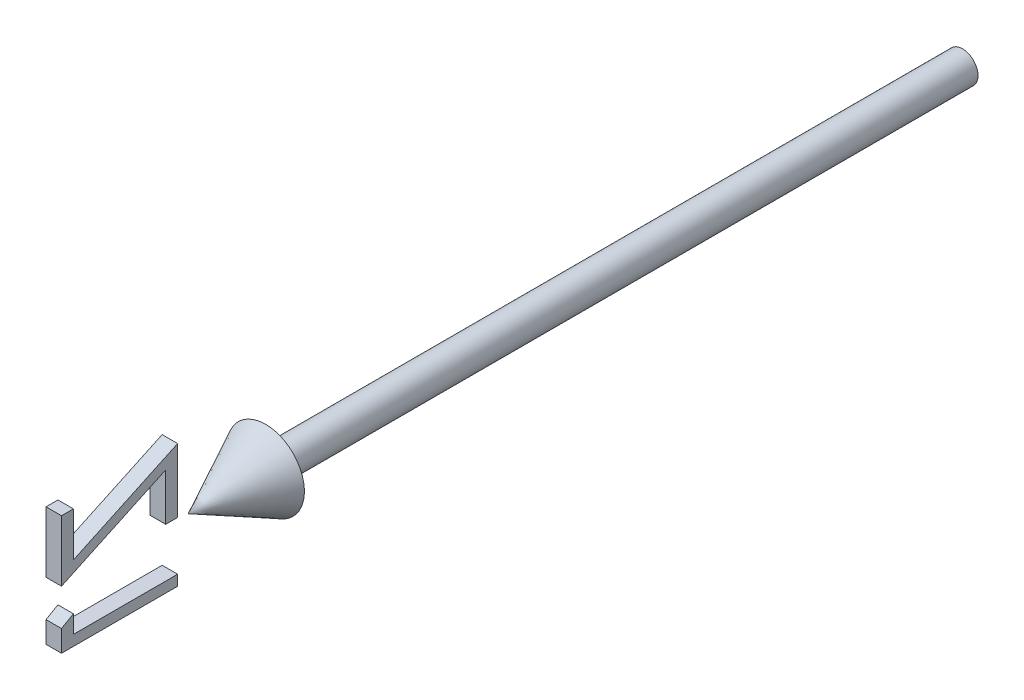
SolidWorks part; units mm, degrees
ref_plane "Front Plane" through (0, 0, 0) normal (0, 0, 1) x (1, 0, 0)
ref_plane "Top Plane" through (0, 0, 0) normal (0, 1, 0) x (1, 0, 0)
ref_plane "Right Plane" through (0, 0, 0) normal (1, 0, 0) x (0, 0, -1)
sketch "Sketch2" plane through (0, 0, 0) normal (0, 1, 0) x (1, 0, 0)
  line L0 (0, 41.95) -> (0, -114.4521) construction
  line L1 (-36.8894, 0) -> (41.4965, 0) construction
  line L2 (0, -100) -> (5, -90)
  line L3 (5, -90) -> (2, -90)
  line L4 (2, -90) -> (2, 0)
  line L5 (2, 0) -> (0, 0)
  line L6 (0, 0) -> (0, -100)
  dimension "D1" = 100
  dimension "D2" = 2
  dimension "D3" = 10
  dimension "D4" = 5
revolve "Revolve1" add sketch "Sketch2" angle 360 about L0
sketch "Sketch3" plane through (0, 0, 0) normal (1, 0, 0) x (0, -1, 0)
  line L0 (0, -101.5706) -> (0, -127.8138) construction
  line L1 (-10.1124, -102.3675) -> (14.1256, -102.3675) construction
  text T0 "Z1" font "Century Gothic" height 15
extrude "Boss-Extrude1" add sketch "Sketch3" against normal blind 1 and the other way blind 1 separate body
equation "\"frame_arrow_length\"=100"
equation "\"D1@Sketch2\"=\"frame_arrow_length\""
equation "\"frame_arrow_odA\"=4"
equation "\"D2@Sketch2\"=\"frame_arrow_odA\"/2"
equation "\"frame_arrow_head_od\"=5"
equation "\"D4@Sketch2\"=\"frame_arrow_head_od\""
equation "\"frame_arrow_head_length\"=10"
equation "\"D3@Sketch2\"=\"frame_arrow_head_length\""
equation "\"tvarobot_theta1\"=30"
equation "\"link0_ringA_odA\"= 40"
equation "\"link0_ringA_odB\"= 25"
equation "\"link0_ringA_id\"= 20"
equation "\"link0_ringA_thickness\"= (\"link0_ringA_odB\" - \"link0_ringA_id\")/2"
equation "\"link0_ringA_height\"= 3"
equation "\"link0_ringA_heightA\"= 1.5"
equation "\"link0_ringA_heightB\"=\"link0_ringA_height\"-\"link0_ringA_heightA\""
equation "\"link0_ringB_odA\"= 40"
equation "\"link0_ringB_odB\"= 29"
equation "\"link0_ringB_id\"= \"link0_shaftA_bearing_id\"+1"
equation "\"link0_ringB_thickness\"= (\"link0_ringB_odB\" - \"link0_ringB_id\")/2"
equation "\"link0_ringB_height\"= 3"
equation "\"link0_ringB_heightA\"= 1.5"
equation "\"link0_ringB_heightB\"=\"link0_ringB_height\"-\"link0_ringB_heightA\""
equation "\"link0_shaftA_bearing_od\"=27"
equation "\"link0_shaftA_bearing_id\"=20"
equation "\"link0_shaftA_thrust_bearing_od\"=35"
equation "\"link0_shaftA_thrust_bearing_id\"=20.04"
equation "\"link0_shaftA_retaining_ring_id\"=18.5"
equation "\"link0_shaftA_retaining_ring_groove_width\"=1.5"
equation "\"link0_shaftA_spline_length\"=8.0"
equation "\"link0_shaftA_spline_depth\"=1.0"
equation "\"link0_shaftA_spline_width\"=4.0"
equation "\"link0_shaftA_odA\"=\"link0_shaftA_bearing_id\""
equation "\"link0_shaftA_odB\"=35"
equation "\"link0_shaftA_odC\"=\"link0_shaftA_bearing_id\""
equation "\"link0_shaftA_odD\"=\"link0_shaftA_odC\"-2*\"link0_shaftA_spline_depth\""
equation "\"link0_shaftA_odE\"=\"link0_shaftA_bearing_id\""
equation "\"link0_shaftA_odF\"=\"link0_shaftA_odE\"-2*\"link0_shaftA_spline_depth\""
equation "\"link0_shaftA_idA\"=10"
equation "\"link0_shaftA_idB\"=6"
equation "\"link0_shaftA_length\"=39.5"
equation "\"link0_shaftA_lengthA\"=8.0"
equation "\"link0_shaftA_lengthB\"=12.0"
equation "\"link0_shaftA_lengthC\"=35.0"
equation "\"link0_shaftA_lengthD\"=39.0"
equation "\"link0_shaftA_lengthE\"=\"link0_shaftA_length\"-\"link0_shaftA_lengthD\""
equation "\"link0_shaftA_offsetX\"=11"
equation "\"link0_shaftA_offsetY\"=0"
equation "\"link0_shaftA_bolt_pattern_dia\"=14"
equation "\"link0_motor_center_dist\"=26"
equation "\"link0_46t_pulley_spline_length\"=8"
equation "\"link0_46t_pulley_spline_depth\"=\"link0_shaftA_spline_depth\"*1.025"
equation "\"link0_46t_pulley_spline_width\"=\"link0_shaftA_spline_width\"*1.05"
equation "\"link0_46t_pulley_idA\"=\"link0_shaftA_bearing_id\"*1.025"
equation "\"link0_46t_pulley_idB\"=\"link0_46t_pulley_idA\"-2*\"link0_46t_pulley_spline_depth\""
equation "\"link0_shaftB_spline_length\"=10"
equation "\"link0_shaftB_spline_depth\"=1.0"
equation "\"link0_shaftB_spline_width\"=1.25"
equation "\"link0_shaftB_length\"=7"
equation "\"link0_shaftB_lengthA\"=1.5"
equation "\"link0_shaftB_lengthB\"=2.75"
equation "\"link0_shaftB_odA\"=32"
equation "\"link0_shaftB_odB\"=22"
equation "\"link0_shaftB_odC\"=20"
equation "\"link0_shaftB_idA\"=10"
equation "\"link0_shaftB_bolt_diameter\"=19"
equation "\"link0_shaftB_bearing_od\"=27"
equation "\"link0_shaftB_bearing_id\"=20"
equation "\"link0_motor_length\"=46.5"
equation "\"link0_motor_width\"=28.5"
equation "\"link0_motor_height\"=34"
equation "\"link0_motor_offset\"=8"
equation "\"link0_shellA_thickness\"=2.5"
equation "\"link0_shellB_thickness\"=\"link0_shellA_thickness\""
equation "\"link0_plateA_shellA_height\"=48"
equation "\"link0_shellA_width\" =\"link0_plateA_width\""
equation "\"link0_shellA_height\" = \"link0_plateA_shellA_height\"-\"link0_plateA_height\""
equation "\"link0_shellA_length\" = \"link0_plateA_lengthB\" "
equation "\"link0_shellB_length\"=\"link0_shellA_length\""
equation "\"link0_shellA_radius\" = 0.375*25.4"
equation "\"link0_shellA_radiusA\"= \"link0_plateA_radiusA\""
equation "\"link0_shellA_radiusB\"= \"link0_plateA_radiusB\""
equation "\"link0_shellA_radiusC\"= 3"
equation "\"link0_postA_height\"=7"
equation "\"link0_postA_width\"=16"
equation "\"link0_postA_length\"=20"
equation "\"link0_postA_posX\"=22"
equation "\"link0_postA_posY\"=17.5"
equation "\"link0_postA_pocket_width\"=6.0"
equation "\"link0_postA_pocket_length\"=2.5"
equation "\"link0_postA_pocket_depth\"=9"
equation "\"link0_postA_pocket_posZ\"=10"
equation "\"link0_postB_height\"=7"
equation "\"link0_postB_width\"=16"
equation "\"link0_postB_length\"=20"
equation "\"link0_postB_posX\"=22"
equation "\"link0_postB_posY\"=17.5"
equation "\"link0_postB_id\"=3.0"
equation "\"link0_postB_pocket_width\"=6.0"
equation "\"link0_postB_pocket_length\"=2.5"
equation "\"link0_postB_pocket_depth\"=9"
equation "\"link0_postB_pocket_posZ\"=10"
equation "\"link0_postC_height\"=7"
equation "\"link0_postC_width\"=16"
equation "\"link0_postC_length\"=20"
equation "\"link0_postC_posX\"=22"
equation "\"link0_postC_posY\"=17.5"
equation "\"link0_postC_id\"=3.0"
equation "\"link0_postC_pocket_width\"=6.0"
equation "\"link0_postC_pocket_length\"=2.5"
equation "\"link0_postC_pocket_depth\"=9"
equation "\"link0_postC_pocket_posZ\"=10"
equation "\"link0_postD_height\"=7"
equation "\"link0_postD_width\"=16"
equation "\"link0_postD_length\"=20"
equation "\"link0_postD_posX\"=22"
equation "\"link0_postD_posY\"=17.5"
equation "\"link0_postD_id\"=3.0"
equation "\"link0_postD_pocket_width\"=6.0"
equation "\"link0_postD_pocket_length\"=3.0"
equation "\"link0_postD_pocket_depth\"=9"
equation "\"link0_postD_pocket_posZ\"=10"
equation "\"link0_postE_height\"=5"
equation "\"link0_postE_width\"=16"
equation "\"link0_postE_length\"=\"link0_plateE_lengthA\"-\"link0_lip_height\""
equation "\"link0_postE_posZ\"=22"
equation "\"link0_postE_posX\"=17.5"
equation "\"link0_postE_posY\"=22"
equation "\"link0_postE_id\"=3.0"
equation "\"link0_postE_cbore_id\"=6.5"
equation "\"link0_postE_hole_id\"=3"
equation "\"link0_postF_posZ\"=22"
equation "\"link0_postF_posX\"=17.5"
equation "\"link0_postF_posY\"=\"link0_plateB_lengthA\"+4"
equation "\"link0_postF_id\"=3.0"
equation "\"link0_postF_cbore_id\"=6.5"
equation "\"link0_postF_hole_id\"=3"
equation "\"link0_postG_posZ\"=22"
equation "\"link0_postG_posX\"=17.5"
equation "\"link0_postG_posY\"=\"link0_plateB_lengthA\"+12"
equation "\"link0_postG_id\"=3.0"
equation "\"link0_postG_cbore_id\"=6.5"
equation "\"link0_postG_hole_id\"=3"
equation "\"link0_postHIJ_posY\"=6"
equation "\"link0_postH_posX\"=28"
equation "\"link0_postH_posY\"=20"
equation "\"link0_postH_posZ\"=20"
equation "\"link0_postH_length\"=10"
equation "\"link0_postI_posX\"=28"
equation "\"link0_postI_posY\"=20"
equation "\"link0_postI_posZ\"=135"
equation "\"link0_postI_length\"=10"
equation "\"link0_postJ_posX\"=28"
equation "\"link0_postJ_posY\"=20"
equation "\"link0_postJ_posZ\"=175"
equation "\"link0_postJ_length\"=10"
equation "\"link0_postK_posX\"=28"
equation "\"link0_postK_posY\"=20"
equation "\"link0_postK_posZ\"=175"
equation "\"link0_postK_length\"=10"
equation "\"link0_postL_posX\"=28"
equation "\"link0_postL_posY\"=20"
equation "\"link0_postL_posZ\"=135"
equation "\"link0_postL_length\"=10"
equation "\"link0_postM_posX\"=28"
equation "\"link0_postM_posY\"=20"
equation "\"link0_postM_posZ\"=35"
equation "\"link0_postM_length\"=10"
equation "\"link0_plateA_lengthA\"=30"
equation "\"link0_plateA_lengthB\"=150"
equation "\"link0_plateA_lengthC\"=30"
equation "\"link0_plateA_length\"=\"link0_plateA_lengthA\"+\"link0_plateA_lengthB\"+\"link0_plateA_lengthC\""
equation "\"link0_plateA_width\"=  68"
equation "\"link0_plateA_height\"= \"link0_plateA_radiusA\""
equation "\"link0_plateA_thickness\"=\"link0_shellA_thickness\""
equation "\"link0_plateA_radius\"= 9.5"
equation "\"link0_plateA_radiusA\"= 18"
equation "\"link0_plateA_radiusB\"= 18"
equation "\"link0_plateA_radiusC\"= 3"
equation "\"link0_plateB_length\"= 40"
equation "\"link0_plateB_width\"= \"link0_plateA_width\"*1.005"
equation "\"link0_plateB_height\"= \"link0_plateA_shellA_height\"*1.005"
equation "\"link0_plateB_lengthA\"=\"link0_lip_height\"+\"link0_plateD_thickness\"+\"link0_motor_mount_thickness\""
equation "\"link0_plateB_lengthB\"=\"link0_plateB_height\"-\"link0_plateB_lengthA\""
equation "\"link0_plateB_radiusA\"= \"link0_plateA_radiusA\""
equation "\"link0_plateB_radiusB\"= \"link0_plateA_radiusB\""
equation "\"link0_plateB_radiusC\"= 3"
equation "\"link0_plateB_idA\"=\"link0_shaftA_odC\"+1"
equation "\"link0_plateB_idB\"=\"link0_shaftA_bearing_od\"-2"
equation "\"link0_plateB_idC\"=\"link0_shaftA_bearing_od\"*1.005"
equation "\"link0_plateB_idD\"=\"link0_shaftA_thrust_bearing_od\"+1 "
equation "\"link0_plateB_depthA\"=1.0"
equation "\"link0_plateB_depthB\"=2.0"
equation "\"link0_plateB_depthC\"=8"
equation "\"link0_plateB_depthD\"=\"link0_plateB_length\"-\"link0_lip_height\"-\"link0_plateD_thickness\" "
equation "\"link0_plateC_length\"=\"link0_plateB_length\""
equation "\"link0_plateC_width\"= \"link0_plateB_width\""
equation "\"link0_plateC_height\"= .1*25.4"
equation "\"link0_plateA_hole_od\" = 0.1*25.4"
equation "\"link0_plateA_hole_delx\" = 0.5*25.4"
equation "\"link0_plateA_hole_delz\" = 0.75*25.4"
equation "\"link0_plateA_hole_offx\" = 0.0*25.4"
equation "\"link0_plateA_hole_offz\" = \"link0_plateA_length\"/2"
equation "\"link0_plateB_hole_od\" = 0.1*25.4"
equation "\"link0_plateB_hole_delx\"= 0.75*25.4"
equation "\"link0_plateB_hole_delz\"= 0.75*25.4"
equation "\"link0_plateB_hole_offx\"= 0.0*25.4"
equation "\"link0_plateB_hole_offz\"= 0.0*25.4"
equation "\"link0_plateC_hole_od\"= 0.1*25.4"
equation "\"link0_plateC_hole_delx\"= 0.75*25.4"
equation "\"link0_plateC_hole_delz\"= 0.75*25.4"
equation "\"link0_plateC_hole_offx\"= 0.0*25.4"
equation "\"link0_plateC_hole_offz\"= 0.0*25.4"
equation "\"link0_plateD_height\"=\"link0_plateB_height\"-2*\"link0_shellA_thickness\""
equation "\"link0_plateD_width\"=\"link0_plateB_width\"-2*\"link0_shellA_thickness\""
equation "\"link0_plateD_thickness\"=10"
equation "\"link0_plateD_radiusA\"=\"link0_plateB_radiusA\"-\"link0_shellA_thickness\""
equation "\"link0_plateD_odA\"= .375*25.4"
equation "\"link0_plateD_odB\"= .375*25.4"
equation "\"link0_plateD_bearing_id\"=20"
equation "\"link0_plateD_bearing_od\"=27"
equation "\"link0_plateE_radiusA\"=\"link0_plateA_radiusA\""
equation "\"link0_plateE_radiusB\"=\"link0_plateA_radiusB\""
equation "\"link0_plateE_radiusC\"=8.0"
equation "\"link0_plateE_length\"=30"
equation "\"link0_plateE_lengthA\"=16"
equation "\"link0_plateE_height\"=\"link0_plateB_height\""
equation "\"link0_plateE_width\"=\"link0_plateB_width\""
equation "\"link0_plateE_odA\"=\"gantry_coupler_id\"*0.99"
equation "\"link0_plateE_idA\"=\"link0_plateE_odA\"-20.0"
equation "\"link0_plateE_spline_depth\"=\"link0_poleA_spline_depth\"*1.05"
equation "\"link0_plateE_spline_width\"=\"link0_poleA_spline_width\"*1.075"
equation "\"link0_plateE_spline_length\"=\"link0_poleA_spline_length\""
equation "\"link0_plateE_coupler_length\"=46"
equation "\"link0_lip_height\"=5.0"
equation "\"link0_lip_thickness\"=2.0"
equation "\"link0_motor_mount_thickness\"=8.0"
equation "\"link0_motor_mount_idA\"=22"
equation "\"link0_motor_mount_idB\"=\"link0_shaftB_bearing_od\"*1.005"
equation "\"link0_motor_mount_idC\"=\"link0_shaftB_bearing_od\"-2"
equation "\"link0_motor_mount_depthA\"=5.5"
equation "\"link0_motor_mount_height\"=\"link0_plateD_height\""
equation "\"link0_motor_mount_width\"=\"link0_plateD_width\""
equation "\"link0_motor_mountL_height\"=36"
equation "\"link0_motor_mountL_heightA\"=12"
equation "\"link0_motor_mountL_length\"=50"
equation "\"link0_motor_mountL_lengthA\"=36"
equation "\"gantry_coupler_od\"=25.4*2.0"
equation "\"gantry_coupler_id\"=1.645*25.4"
equation "\"gantry_coupler_offsetX\"=\"link0_plateE_width\"/2"
equation "\"link0_poleA_odA\"=20"
equation "\"link0_poleA_odB\"=36"
equation "\"link0_poleA_idA\"=\"link0_poleA_odA\"-2*\"link0_poleA_thickness\""
equation "\"link0_poleA_idB\"=(\"link0_plateE_idA\"/2+1.5*\"link0_lip_thickness\")*1.04"
equation "\"link0_poleA_thickness\"=3.5"
equation "\"link0_poleA_length\"=100"
equation "\"link0_poleA_lengthA\"=18.5"
equation "\"link0_poleA_lengthB\"=80"
equation "\"link0_poleA_gasket_thickness\"=1.5"
equation "\"link0_poleA_spline_depth\"=1.0"
equation "\"link0_poleA_spline_width\"=4.0"
equation "\"link0_poleA_spline_length\"=10.0"
equation "\"link1_plateB_length\"=30"
equation "\"link1_lip_height\"=\"link0_lip_height\""
equation "\"link0_tension_plateA_width\"=12"
equation "\"link0_tension_plateA_lengthA\"=10.5"
equation "\"link0_tension_plateB_width\"=\"link0_tension_plateA_width\""
equation "\"link0_tension_plateB_lengthA\"=\"link0_tension_plateA_lengthA\""
equation "\"link0_tension_wheelA_posZ\"=7"
equation "\"link0_tension_wheelA_posX\"=\"link0_plateD_height\"/2-\"link0_tension_plateA_lengthA\""
equation "\"link0_m2_clear_hole_id\"=2.35"
equation "\"link0_m2_insert_hole_id\"=2.5"
equation "\"link0_m2_tap_hole_id\"=1.75"
equation "\"link0_m2_nut_socket_width\"=4.25"
equation "\"link0_m2_nut_socket_depth\"=2.5"
equation "\"link0_m2_cbore_id\"=3.75"
equation "\"link0_m2_cbore_depth\"=7"
equation "\"link0_m2_5_clear_hole_id\"=2.75"
equation "\"link0_m2_5_insert_hole_id\"=2.75"
equation "\"link0_m2_5_tap_hole_id\"=2.25"
equation "\"link0_m2_5_nut_socket_width\"=5.25"
equation "\"link0_m2_5_nut_socket_depth\"=2.5"
equation "\"link0_m2_5_cbore_id\"=4.75"
equation "\"link0_m2_5_cbore_depth\"=2.5"
equation "\"link0_m2_5_insert_access_length\"=6.0"
equation "\"link0_m2_5_insert_access_width\"=3.0"
equation "\"link0_m3_clear_hole_id\"=3.25"
equation "\"link0_m3_insert_hole_id\"=3"
equation "\"link0_m3_tap_hole_id\"=2.75"
equation "\"link0_m3_nut_socket_width\"=5.75"
equation "\"link0_m3_nut_socket_depth\"=4.0"
equation "\"link0_m3_cbore_id\"=5.75"
equation "\"link0_m3_cbore_depth\"=3.5"
equation "\"link0_m3_insert_access_length\"=4.5"
equation "\"link0_m3_insert_access_width\"=3.5"
equation "\"link0_rpi_mount_height\"=6"
equation "\"link0_rpi_mount_width\"=49"
equation "\"link0_rpi_mount_length\"=58"
equation "\"link0_rpi_mount_post_od\"=6"
equation "\"link0_rpi_mount_posZ\"=72"
equation "\"link0_rpi_mount_posX\"=11.5"
equation "\"link0_mcu_mount_height\"=5"
equation "\"link0_mcu_mount_width\"=49"
equation "\"link0_mcu_mount_length\"=58"
equation "\"link0_mcu_mount_post_od\"=6"
equation "\"link0_mcu_mount_posZ\"=164"
equation "\"link0_mcu_mount_posX\"=4"
equation "\"link0_pwr_mount_height\"=4"
equation "\"link0_pwr_mount_width\"=15.75"
equation "\"link0_pwr_mount_length\"=75.75"
equation "\"link0_pwr_mount_post_od\"=6"
equation "\"link0_pwr_mount_posZ\"=75"
equation "\"link0_pwr_mount_posX\"=16"
equation "\"link0_pwr_board_height\"=6"
equation "\"link0_pwr_board_width\"=21"
equation "\"link0_pwr_board_length\"=80"
